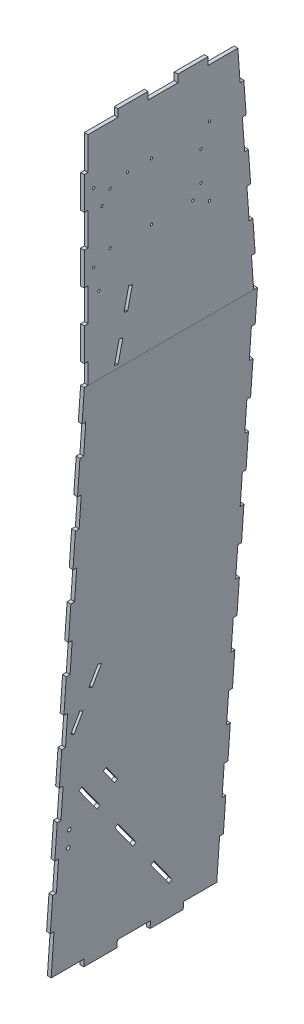
SolidWorks part; units mm, degrees
material "A-Glass Fiber"
ref_plane "Front Plane" through (0, 0, 0) normal (0, 0, 1) x (1, 0, 0)
ref_plane "Top Plane" through (0, 0, 0) normal (0, 1, 0) x (1, 0, 0)
ref_plane "Right Plane" through (0, 0, 0) normal (1, 0, 0) x (0, 0, -1)
sketch "Sketch1" plane through (0, 0, 0) normal (0, 0, 1) x (1, 0, 0)
  line L0 (-215.8818, 2052.32) -> (-215.8818, 1463.04)
  line L1 (-215.8818, 1463.04) -> (-316.0886, 20.32)
  line L2 (-316.0886, 20.32) -> (-317.5, 0)
  line L4 (-215.8818, 2052.32) -> (-215.8818, 2072.64)
  line L6 (-215.8818, 2072.64) -> (-205.7153, 2072.64)
  line L7 (-205.7153, 2072.64) -> (-205.7153, 1463.04)
  line L8 (-205.7153, 1463.04) -> (-307.3335, 0)
  line L9 (-317.5, 0) -> (-307.3335, 0)
  line L10 (-371.5407, 0) -> (-280.9748, 0) construction
  line L13 (-371.5407, 20.32) -> (-280.9748, 20.32) construction
  line L15 (-205.7153, 1463.04) -> (205.7153, 1463.04) construction
  point P23 (-305.9221, 20.32)
  dimension "D1" = 307.3335
extrude "Boss-Extrude1" add sketch "Sketch1" against normal blind 469.9
sketch "Sketch2" plane through (-315.9757, 21.9467, 0) normal (-0.9976, 0.0693, 0) x (0, 0, 1)
  line L35 (0, 1355.6785) -> (0, 0.1049)
  line L37 (-234.95, 1444.5652) -> (-234.95, -21.9996) construction
  line L40 (-10.16, 0.1049) -> (0, 0.1049)
  line L43 (-10.16, 0.1049) -> (-10.16, -21.9996)
  line L46 (0, 1272.0274) -> (-10.16, 1272.0274)
  line L47 (-10.16, 1355.6785) -> (-10.16, 1272.0274)
  line L48 (0, 1355.6785) -> (-10.16, 1355.6785)
  line L49 (0, 1177.9051) -> (-10.16, 1177.9051)
  line L50 (-10.16, 1177.9051) -> (-10.16, 1094.2274)
  line L51 (0, 1094.2274) -> (-10.16, 1094.2274)
  line L52 (0, 916.4274) -> (-10.16, 916.4274)
  line L53 (-10.16, 1000.1317) -> (-10.16, 916.4274)
  line L54 (0, 1000.1317) -> (-10.16, 1000.1317)
  line L55 (0, 822.3583) -> (-10.16, 822.3583)
  line L56 (0, 738.6274) -> (-10.16, 738.6274)
  line L57 (-10.16, 822.3583) -> (-10.16, 738.6274)
  line L58 (0, 644.5849) -> (-10.16, 644.5849)
  line L59 (-10.16, 644.5849) -> (-10.16, 560.8274)
  line L60 (0, 560.8274) -> (-10.16, 560.8274)
  line L61 (0, 466.8115) -> (-10.16, 466.8115)
  line L62 (-10.16, 466.8115) -> (-10.16, 383.0274)
  line L63 (0, 383.0274) -> (-10.16, 383.0274)
  line L64 (0, 289.0381) -> (-10.16, 289.0381)
  line L65 (-10.16, 289.0381) -> (-10.16, 205.2274)
  line L66 (0, 205.2274) -> (-10.16, 205.2274)
  line L67 (0, 111.2647) -> (-10.16, 111.2647)
  line L68 (-10.16, 111.2647) -> (-10.16, 0.1049)
  line L69 (0, 0.1049) -> (-10.16, 0.1049)
  line L70 (-10.16, -21.9996) -> (0, -21.9996)
  line L71 (0, 0.1049) -> (0, -21.9996)
  line L72 (-469.9, 1444.5652) -> (0, 1444.5652) construction
  line L73 (-469.9, -21.9996) -> (0, -21.9996) construction
  line L74 (-469.9, 0.1049) -> (-469.9, -21.9996)
  line L75 (-459.74, -21.9996) -> (-469.9, -21.9996)
  line L76 (-469.9, 0.1049) -> (-459.74, 0.1049)
  line L77 (-459.74, 111.2647) -> (-459.74, 0.1049)
  line L78 (-469.9, 111.2647) -> (-459.74, 111.2647)
  line L79 (-469.9, 205.2274) -> (-459.74, 205.2274)
  line L80 (-459.74, 289.0381) -> (-459.74, 205.2274)
  line L81 (-469.9, 289.0381) -> (-459.74, 289.0381)
  line L82 (-469.9, 383.0274) -> (-459.74, 383.0274)
  line L83 (-459.74, 466.8115) -> (-459.74, 383.0274)
  line L84 (-469.9, 466.8115) -> (-459.74, 466.8115)
  line L85 (-469.9, 560.8274) -> (-459.74, 560.8274)
  line L86 (-459.74, 644.5849) -> (-459.74, 560.8274)
  line L87 (-469.9, 644.5849) -> (-459.74, 644.5849)
  line L88 (-459.74, 822.3583) -> (-459.74, 738.6274)
  line L89 (-469.9, 738.6274) -> (-459.74, 738.6274)
  line L90 (-469.9, 822.3583) -> (-459.74, 822.3583)
  line L91 (-469.9, 1000.1317) -> (-459.74, 1000.1317)
  line L92 (-459.74, 1000.1317) -> (-459.74, 916.4274)
  line L93 (-469.9, 916.4274) -> (-459.74, 916.4274)
  line L94 (-469.9, 1094.2274) -> (-459.74, 1094.2274)
  line L95 (-459.74, 1177.9051) -> (-459.74, 1094.2274)
  line L96 (-469.9, 1177.9051) -> (-459.74, 1177.9051)
  line L97 (-469.9, 1355.6785) -> (-459.74, 1355.6785)
  line L98 (-459.74, 1355.6785) -> (-459.74, 1272.0274)
  line L99 (-469.9, 1272.0274) -> (-459.74, 1272.0274)
  line L100 (-459.74, 0.1049) -> (-459.74, -21.9996)
  line L101 (-459.74, 0.1049) -> (-469.9, 0.1049)
  line L102 (-469.9, 1355.6785) -> (-469.9, 0.1049)
  line L103 (-469.9, 1444.5652) -> (-469.9, -21.9996) construction
  line L104 (-459.74, 205.2274) -> (-469.9, 205.2274) construction
  line M1 (0, -21.9996) -> (0, 1444.5652)
  line M3 (-469.9, 1444.5652) -> (-469.9, -21.9996)
  line M4 (-469.9, -21.9996) -> (0, -21.9996)
extrude "Cut-Extrude1" cut sketch "Sketch2" against normal blind 10.16 contours L66 L35 L64 L65 | L69 L67 L68 M1 | L60 L35 L58 L59 | L63 L35 L61 L62 | L55 L57 L56 L35 | L35 L54 L53 L52 | L51 L35 L49 L50 | L35 L48 L47 L46 | L40 L43 M4 M1 | L100 L76 M3 M4 | L78 L76 L77 M3 | L81 L79 L80 M3 | L84 L82 L83 M3 | L87 L85 L86 M3 | L90 L89 L88 M3 | L93 L92 L91 M3 | L96 L94 L95 M3 | L99 L98 L97 M3 region at (-224.9388, 1332.6419, -464.82) region at (-237.2577, 1155.2825, -464.82) region at (-249.5765, 977.9231, -464.82) region at (-261.8953, 800.5637, -464.82) region at (-274.2142, 623.2043, -464.82) region at (-286.533, 445.8449, -464.82) region at (-298.8518, 268.4855, -464.82) region at (-316.7342, 11.0257, -464.82) region at (-312.1173, 77.4977, -5.08) region at (-298.8518, 268.4855, -5.08) region at (-286.533, 445.8449, -5.08) region at (-274.2142, 623.2043, -5.08) region at (-261.8953, 800.5637, -5.08) region at (-249.5765, 977.9231, -5.08) region at (-237.2577, 1155.2825, -5.08) region at (-224.9388, 1332.6419, -5.08) region at (-316.7342, 11.0257, -5.08) region at (-312.1173, 77.4977, -464.82)
sketch "Sketch3" plane through (-215.8818, 0, 0) normal (-1, 0, 0) x (0, 0, 1)
  line L0 (0, 2052.32) -> (-10.16, 2052.32) construction
  line L1 (0, 1963.42) -> (-10.16, 1963.42) construction
  line L2 (-10.16, 2052.32) -> (-10.16, 1963.42) construction
  line L3 (0, 1874.52) -> (-10.16, 1874.52) construction
  line L4 (0, 1463.04) -> (0, 2072.64)
  line L5 (0, 2072.64) -> (-469.9, 2072.64)
  line L6 (-469.9, 2072.64) -> (-469.9, 1463.04)
  line L8 (0, 1463.04) -> (0, 2072.64)
  line L9 (0, 2072.64) -> (-469.9, 2072.64)
  line L12 (0, 1785.62) -> (-10.16, 1785.62) construction
  line L13 (-10.16, 1874.52) -> (-10.16, 1785.62) construction
  line L14 (0, 1696.72) -> (-10.16, 1696.72) construction
  line L15 (0, 1607.82) -> (-10.16, 1607.82) construction
  line L16 (-10.16, 1696.72) -> (-10.16, 1607.82) construction
  line L17 (0, 1518.92) -> (-10.16, 1518.92) construction
  line L18 (-10.16, 1518.92) -> (-10.16, 1488.44) construction
  line L19 (0, 2052.32) -> (-10.16, 2052.32)
  line L20 (0, 1963.42) -> (-10.16, 1963.42)
  line L21 (-10.16, 2052.32) -> (-10.16, 1963.42)
  line L22 (0, 1874.52) -> (-10.16, 1874.52)
  line L23 (0, 1785.62) -> (-10.16, 1785.62)
  line L24 (-10.16, 1874.52) -> (-10.16, 1785.62)
  line L25 (0, 1696.72) -> (-10.16, 1696.72)
  line L26 (0, 1607.82) -> (-10.16, 1607.82)
  line L27 (-10.16, 1696.72) -> (-10.16, 1607.82)
  line L28 (0, 1518.92) -> (-10.16, 1518.92)
  line L29 (-10.16, 1518.92) -> (-10.16, 1488.44)
  line L30 (0, 2052.32) -> (0, 1463.04)
  line L31 (-234.95, 1463.04) -> (-234.95, 2072.64) construction
  line L32 (-10.16, 2052.32) -> (0, 2052.32)
  line L33 (-10.16, 2052.32) -> (-10.16, 2072.64)
  line L34 (-10.16, 2072.64) -> (0, 2072.64)
  line L35 (0, 2052.32) -> (0, 2072.64)
  line L36 (-469.9, 1463.04) -> (-425.45, 2072.64)
  line L37 (-469.9, 1463.04) -> (-463.754, 1547.3284)
  line L38 (-469.9, 1463.04) -> (-459.7669, 1462.3011)
  line L39 (-463.754, 1547.3284) -> (-453.6209, 1546.5895)
  line L40 (-459.7669, 1462.3011) -> (-453.6209, 1546.5895)
  line L41 (-463.754, 1547.3284) -> (-453.6209, 1546.5895)
  line L42 (-463.754, 1547.3284) -> (-457.6079, 1631.6168)
  line L43 (-453.6209, 1546.5895) -> (-447.4748, 1630.8779)
  line L44 (-457.6079, 1631.6168) -> (-447.4748, 1630.8779)
  line L45 (-457.6079, 1631.6168) -> (-447.4748, 1630.8779)
  line L46 (-457.6079, 1631.6168) -> (-451.4619, 1715.9052)
  line L47 (-447.4748, 1630.8779) -> (-441.3288, 1715.1664)
  line L48 (-451.4619, 1715.9052) -> (-441.3288, 1715.1664)
  line L49 (-451.4619, 1715.9052) -> (-441.3288, 1715.1664)
  line L50 (-451.4619, 1715.9052) -> (-445.3159, 1800.1936)
  line L51 (-441.3288, 1715.1664) -> (-435.1828, 1799.4548)
  line L52 (-445.3159, 1800.1936) -> (-435.1828, 1799.4548)
  line L53 (-445.3159, 1800.1936) -> (-435.1828, 1799.4548)
  line L54 (-10.16, 1488.44) -> (-10.16, 1463.04)
  line L56 (-445.3159, 1800.1936) -> (-439.1699, 1884.4821)
  line L57 (-435.1828, 1799.4548) -> (-429.0368, 1883.7432)
  line L58 (-439.1699, 1884.4821) -> (-429.0368, 1883.7432)
  line L59 (-439.1699, 1884.4821) -> (-429.0368, 1883.7432)
  line L60 (-439.1699, 1884.4821) -> (-433.0238, 1968.7705)
  line L61 (-429.0368, 1883.7432) -> (-422.8907, 1968.0316)
  line L62 (-433.0238, 1968.7705) -> (-422.8907, 1968.0316)
  line L63 (-10.16, 2052.32) -> (-469.9, 2052.32) construction
  line L64 (-469.9, 2072.64) -> (-469.9, 1463.04) construction
  line L65 (-433.0238, 1968.7705) -> (-422.8907, 1968.0316)
  line L66 (-433.0238, 1968.7705) -> (-426.8778, 2053.0589)
  line L67 (-422.8907, 1968.0316) -> (-416.7447, 2052.32)
  line L68 (-426.8778, 2053.0589) -> (-416.7447, 2052.32)
  line L69 (-416.7447, 2052.32) -> (-426.9317, 2052.32)
  line L70 (-426.8778, 2053.0589) -> (-416.7447, 2052.32)
  line L71 (-426.8778, 2053.0589) -> (-425.3531, 2073.9694)
  line L72 (-416.7447, 2052.32) -> (-415.22, 2073.2306)
  line L73 (-425.3531, 2073.9694) -> (-415.22, 2073.2306)
  line L74 (-469.9, 1463.04) -> (0, 1463.04) construction
  line L78 (-469.9, 1463.04) -> (0, 1463.04)
  line L79 (-469.9, 1463.04) -> (0, 1463.04)
  line M7 (0, 1463.04) -> (0, 2072.64)
  line M8 (0, 2072.64) -> (-469.9, 2072.64)
  line M9 (-469.9, 2072.64) -> (-469.9, 1463.04)
  line M10 (-469.9, 1463.04) -> (0, 1463.04)
  dimension "D2" = 44.45
  dimension "D3" = 10.16
  dimension "D1" = 0
extrude "Cut-Extrude2" cut sketch "Sketch3" against normal blind 12.7 contours M10 | L29 L54 L28 M10 M7 | L36 L66 M9 M8 | L48 L36 L44 L47 | L58 L36 L52 L57 | L67 L69 L36 L62 | L25 L27 L26 L8 | L22 L24 L23 L8 | L19 L21 L20 L8 | L33 L19 L8 M8 | L68 L72 L36 M8 | L69 L68 L66 region at (-215.8818, 1490.98, -5.08) region at (-215.8818, 1652.27, -5.08) region at (-215.8818, 1504.9998, -461.7544) region at (-215.8818, 1869.44, -455.0833) region at (-215.8818, 1830.07, -5.08) region at (-215.8818, 1673.3916, -449.4684) region at (-215.8818, 2062.6636, -421.0525) region at (-215.8818, 2007.87, -5.08) region at (-215.8818, 1841.9684, -437.1763) region at (-215.8818, 2052.5663, -423.5181) region at (-215.8818, 2062.48, -5.08) region at (-215.8818, 2010.3602, -424.8903)
sketch "Sketch4" plane through (-215.8818, 0, 0) normal (-1, 0, 0) x (0, 0, 1)
  line L1 (-416.7447, 2072.64) -> (-335.4278, 2072.64)
  line L2 (-416.7447, 2072.64) -> (-416.7447, 2052.32)
  line L3 (-416.7447, 2052.32) -> (-335.4278, 2052.32)
  line L4 (-335.4278, 2072.64) -> (-335.4278, 2052.32)
  line L5 (-10.16, 2072.64) -> (-10.16, 1963.42) construction
  line L6 (-335.4278, 2072.64) -> (-254.1108, 2072.64)
  line L7 (-335.4278, 2072.64) -> (-335.4278, 2052.32)
  line L8 (-335.4278, 2052.32) -> (-254.1108, 2052.32)
  line L9 (-254.1108, 2072.64) -> (-254.1108, 2052.32)
  line L10 (-254.1108, 2072.64) -> (-172.7939, 2072.64)
  line L11 (-254.1108, 2072.64) -> (-254.1108, 2052.32)
  line L12 (-254.1108, 2052.32) -> (-172.7939, 2052.32)
  line L13 (-172.7939, 2072.64) -> (-172.7939, 2052.32)
  line L14 (-172.7939, 2072.64) -> (-91.4769, 2072.64)
  line L15 (-172.7939, 2072.64) -> (-172.7939, 2052.32)
  line L16 (-172.7939, 2052.32) -> (-91.4769, 2052.32)
  line L17 (-91.4769, 2072.64) -> (-91.4769, 2052.32)
  line L18 (-91.4769, 2072.64) -> (-10.16, 2072.64)
  line L19 (-91.4769, 2072.64) -> (-91.4769, 2052.32)
  line L20 (-91.4769, 2052.32) -> (-10.16, 2052.32)
  line L21 (-10.16, 2072.64) -> (-10.16, 2052.32)
  line L23 (-422.8907, 1968.0316) -> (-415.263, 2072.64) construction
  line L24 (-415.263, 2072.64) -> (-10.16, 2072.64) construction
  line M26 (-10.16, 1963.42) -> (-10.16, 2072.64)
  line M27 (-10.16, 2072.64) -> (-415.263, 2072.64)
  dimension "D1" = 20.32
extrude "Cut-Extrude3" cut sketch "Sketch4" against normal blind 12.7 contours L4 L3 M27 | L13 L9 L12 M27 | L17 L20 M26 M27 region at (-215.8818, 2062.48, -376.0862) region at (-215.8818, 2062.48, -213.4523) region at (-215.8818, 2062.48, -50.8185)
sketch "Sketch5" plane through (-315.9757, 21.9467, 0) normal (-0.9976, 0.0693, 0) x (0, 0, 1)
  line L1 (-459.74, -21.9996) -> (-369.824, -21.9996)
  line L2 (-459.74, -21.9996) -> (-459.74, -1.6796)
  line L3 (-459.74, -1.6796) -> (-369.824, -1.6796)
  line L4 (-369.824, -21.9996) -> (-369.824, -1.6796)
  line L5 (-369.824, -21.9996) -> (-279.908, -21.9996)
  line L6 (-369.824, -21.9996) -> (-369.824, -1.6796)
  line L7 (-369.824, -1.6796) -> (-279.908, -1.6796)
  line L8 (-279.908, -21.9996) -> (-279.908, -1.6796)
  line L9 (-279.908, -21.9996) -> (-189.992, -21.9996)
  line L10 (-279.908, -21.9996) -> (-279.908, -1.6796)
  line L11 (-279.908, -1.6796) -> (-189.992, -1.6796)
  line L12 (-189.992, -21.9996) -> (-189.992, -1.6796)
  line L13 (-189.992, -21.9996) -> (-100.076, -21.9996)
  line L14 (-189.992, -21.9996) -> (-189.992, -1.6796)
  line L15 (-189.992, -1.6796) -> (-100.076, -1.6796)
  line L16 (-100.076, -21.9996) -> (-100.076, -1.6796)
  line L17 (-100.076, -21.9996) -> (-10.16, -21.9996)
  line L18 (-100.076, -21.9996) -> (-100.076, -1.6796)
  line L19 (-100.076, -1.6796) -> (-10.16, -1.6796)
  line L20 (-10.16, -21.9996) -> (-10.16, -1.6796)
  line L21 (-10.16, 111.2647) -> (-10.16, -21.9996) construction
  dimension "D1" = 20.32
extrude "Cut-Extrude4" cut sketch "Sketch5" against normal blind 12.7 contours L1 L4 L3 L2 | L9 L12 L11 L8 | L17 L20 L19 L18 L16 region at (-316.796, 10.1356, -414.782) region at (-316.796, 10.1356, -234.95) region at (-316.796, 10.1356, -55.118)
sketch "Sketch6" plane through (-315.9757, 21.9467, 0) normal (-0.9976, 0.0693, 0) x (0, 0, 1)
  line L0 (-217.3726, 211.9965) -> (-163.4402, 285.2141)
  line L1 (-325.2304, 65.5562) -> (-271.298, 138.7738)
  line L2 (-44.1085, 632.6765) -> (-22.5289, 586.4358) construction
  line L3 (-74.8989, 674.6188) -> (-65.6881, 678.9173) construction
  line L8 (-271.6486, 139.032) -> (-279.8219, 145.0526) construction
  line L56 (-87.2678, 725.158) -> (-65.6881, 678.9173) construction
  line L57 (-74.8989, 674.6188) -> (-96.4785, 720.8595) construction
  line L58 (-31.7396, 582.1373) -> (-22.5289, 586.4358) construction
  line L59 (-31.7396, 582.1373) -> (-53.3192, 628.3781) construction
  line L60 (-53.3192, 628.3781) -> (-44.1085, 632.6765) construction
  line L63 (-117.6881, 364.4573) -> (-63.7557, 437.6749) construction
  line L65 (-225.5528, 218.0222) -> (-171.6205, 291.2397) construction
  line L69 (-333.4176, 71.587) -> (-279.4852, 144.8046) construction
  line L70 (-109.5008, 358.4266) -> (-55.5685, 431.6442)
  line L71 (-44.1085, 632.6765) -> (-22.5289, 586.4358)
  line L72 (-74.8989, 674.6188) -> (-65.6881, 678.9173)
  line L73 (-87.2678, 725.158) -> (-65.6881, 678.9173)
  line L74 (-74.8989, 674.6188) -> (-96.4785, 720.8595)
  line L75 (-31.7396, 582.1373) -> (-22.5289, 586.4358)
  line L76 (-31.7396, 582.1373) -> (-53.3192, 628.3781)
  line L77 (-53.3192, 628.3781) -> (-44.1085, 632.6765)
  line L78 (-109.5008, 358.4266) -> (-117.6881, 364.4573)
  line L79 (-55.5685, 431.6442) -> (-63.7557, 437.6749)
  line L80 (-117.6881, 364.4573) -> (-63.7557, 437.6749)
  line L81 (-163.4402, 285.2141) -> (-171.6205, 291.2397)
  line L82 (-225.5528, 218.0222) -> (-171.6205, 291.2397)
  line L83 (-217.3726, 211.9965) -> (-225.5528, 218.0222)
  line L84 (-271.298, 138.7738) -> (-279.4852, 144.8046)
  line L85 (-325.2304, 65.5562) -> (-333.4176, 71.587)
  line L86 (-333.4176, 71.587) -> (-279.4852, 144.8046)
  line L87 (-87.2678, 725.158) -> (-96.4785, 720.8595)
  line L89 (-109.8514, 358.6848) -> (-118.0248, 364.7053) construction
  line L90 (-163.7838, 285.4672) -> (-171.9572, 291.4877) construction
  line L91 (-217.7162, 212.2496) -> (-225.8895, 218.2702) construction
  dimension "D1" = 10.16
extrude "Cut-Extrude5" cut sketch "Sketch6" against normal blind 137.414 contours L73 L87 L74 L72 | L77 L76 L75 L71 | L80 L78 | L83 L81 L82 | L86 L85 L84 region at (-298.541, 272.9601, -194.4965) region at (-308.6877, 126.8743, -302.3578) region at (-288.3947, 419.0407, -86.6283) region at (-273.8885, 627.8938, -37.9241) region at (-267.4804, 720.1529, -81.0833)
sketch "Sketch8" plane through (-215.8818, 0, 0) normal (-1, 0, 0) x (0, 0, 1)
  circle A0 centre (-450.215, 1043.94) radius 9.525 construction
  circle A1 centre (-450.215, 1043.94) radius 9.525
sketch "Sketch13" plane through (-215.8818, 0, 0) normal (-1, 0, 0) x (0, 0, 1)
  line L0 (-413.556, 1633.6344) -> (-413.556, 1614.5844) construction
  line L1 (-270.8715, 1611.4094) -> (-270.8715, 1636.8094) construction
  line L2 (-413.556, 1624.1094) -> (-270.8715, 1624.1094) construction
  line L3 (-270.8715, 1624.1094) -> (-400.856, 1624.1094) construction
  line L4 (-270.8715, 1605.0594) -> (-400.856, 1605.0594) construction
  line L5 (-270.8715, 1643.1594) -> (-400.856, 1643.1594) construction
  line L6 (-416.7447, 2052.32) -> (-335.4278, 2052.32)
  line L7 (-422.8907, 1968.0316) -> (-416.7447, 2052.32)
  circle A0 centre (-25.2465, 1731.87) radius 3.175
  circle A1 centre (-70.409, 1755.42) radius 3.175
  circle A2 centre (-182.409, 1755.42) radius 3.175
  circle A3 centre (-25.2465, 1918.97) radius 3.175
  circle A4 centre (-47.789, 1865.42) radius 3.175
  circle A5 centre (-182.409, 1910.42) radius 3.175
  circle A6 centre (-117.079, 1910.42) radius 3.175
  circle A7 centre (-70.409, 1895.42) radius 3.175
  circle A8 centre (-317.029, 1865.42) radius 3.175
  circle A9 centre (-294.409, 1755.42) radius 3.175
  circle A10 centre (-317.029, 1785.42) radius 3.175
  circle A11 centre (-339.5715, 1731.87) radius 3.175
  circle A12 centre (-339.5715, 1918.97) radius 3.175
  arc A13 (-270.8715, 1605.0594) -> (-270.8715, 1643.1594) centre (-270.8715, 1624.1094) ccw construction
  arc A14 (-400.856, 1643.1594) -> (-400.856, 1605.0594) centre (-400.856, 1624.1094) ccw construction
  point P34 (-335.8637, 1624.1094)
  point P42 (-416.7447, 2052.32)
  dimension "D1" = 12.7
  dimension "D2" = 19.05
extrude "Cut-Extrude8" cut sketch "Sketch13" against normal through all contours L5 A14 L4 A13 | A11 | A10 | A9 | A2 | A1 | A0 | A4 | A7 | A6 | A3 | A5 | A8 | A12 | L0 A14 region at (-215.8818, 1731.87, -25.2465) region at (-215.8818, 1755.42, -70.409) region at (-215.8818, 1755.42, -182.409) region at (-215.8818, 1918.97, -25.2465) region at (-215.8818, 1865.42, -47.789) region at (-215.8818, 1910.42, -182.409) region at (-215.8818, 1910.42, -117.079) region at (-215.8818, 1895.42, -70.409) region at (-215.8818, 1865.42, -317.029) region at (-215.8818, 1755.42, -294.409) region at (-215.8818, 1785.42, -317.029) region at (-215.8818, 1731.87, -339.5715) region at (-215.8818, 1918.97, -339.5715)
sketch "Sketch17" plane through (-215.8818, 0, 0) normal (-1, 0, 0) x (0, 0, 1)
  line L0 (-130.4243, 1639.6605) -> (-120.5247, 1641.946)
  line L1 (-120.5247, 1641.946) -> (-107.584, 1585.8939)
  line L2 (-130.4243, 1639.6605) -> (-117.4836, 1583.6084)
  line L3 (-117.4836, 1583.6084) -> (-107.584, 1585.8939)
  line L4 (-104.543, 1527.5563) -> (-94.6434, 1529.8418)
  line L5 (-91.6023, 1471.5043) -> (-104.543, 1527.5563)
  line L6 (-91.6023, 1471.5043) -> (-81.7027, 1473.7898)
  line L7 (-81.7027, 1473.7898) -> (-94.6434, 1529.8418)
  line L8 (-416.7447, 2052.32) -> (-335.4278, 2052.32)
  line L9 (-422.8907, 1968.0316) -> (-416.7447, 2052.32)
  point P11 (-416.7447, 2052.32)
extrude "Cut-Extrude9" cut sketch "Sketch17" against normal through all contours L6 L7 L4 L5 | L2 L3 L1 L0 region at (-215.8818, 1612.7772, -119.0041) region at (-215.8818, 1500.6731, -93.1229)
sketch "Sketch20" plane through (-315.9757, 21.9467, 0) normal (-0.9976, 0.0693, 0) x (0, 0, 1)
  line L0 (-441.6805, 375.8656) -> (-258.1103, 563.7707)
  line L1 (-258.1103, 563.7707) -> (-341.7803, 797.9819)
  line L2 (-258.1103, 563.7707) -> (-10.16, 315.8204)
  line L3 (-258.1103, 563.7707) -> (-258.6478, 797.9819)
  line L8 (-10.16, 110.1771) -> (-10.16, -1.6796)
  line L9 (-10.16, 466.8115) -> (-10.16, 383.0274) construction
  line L10 (-13.335, 290.1376) -> (-13.335, 359.9876)
  line L11 (-13.335, 290.1376) -> (-48.26, 290.1376)
  line L12 (-13.335, 359.9876) -> (-48.26, 359.9876)
  line L13 (-48.26, 290.1376) -> (-48.26, 359.9876)
  line L32 (-120.9293, 445.7124) -> (-154.8235, 399.6982)
  line L33 (-120.9293, 445.7124) -> (-128.5983, 451.3614)
  line L34 (-154.8235, 399.6982) -> (-162.4926, 405.3473)
  line L35 (-128.5983, 451.3614) -> (-162.4926, 405.3473)
  line L37 (-109.5008, 358.4266) -> (-117.6881, 364.4573) construction
  line L38 (-117.6881, 364.4573) -> (-63.7557, 437.6749) construction
  line L39 (-137.8764, 422.7053) -> (43.6586, 288.9858) construction
  line L40 (-35.56, 332.8883) -> (-35.56, 361.687) construction
  line L41 (-10.16, 466.8115) -> (-10.16, 383.0274)
  circle A0 centre (-35.56, 347.2876) radius 4.7625
  circle A2 centre (-35.56, 302.8376) radius 4.7625
  point P11 (-10.16, -1.6796)
  point P57 (-35.56, 341.2204)
  dimension "D9" = 44.45
  dimension "D15" = 9.525
  dimension "D3" = 3.175
  dimension "D4" = 12.7
  dimension "D5" = 57.15
  dimension "D6" = 317.5
  dimension "D7" = 12.7
  dimension "D8" = 12.7
  dimension "D22" = 9.525
  dimension "D23" = 6.35
  dimension "D24" = 50.8
  dimension "D25" = 34.925
extrude "Cut-Extrude10" cut sketch "Sketch20" against normal through all contours A2 | L2 A0 | L2 A0 | L2 L35 L34 L32 | L33 L35 L2 L32 region at (-285.2619, 464.1454, -128.5379) region at (-286.8509, 441.2683, -145.572) region at (-291.908, 368.4591, -35.5004) region at (-292.1316, 365.2395, -38.7278) region at (-294.992, 324.0565, -35.56)
sketch "Sketch22" [suppressed] plane through (-315.9757, 21.9467, 0) normal (-0.9976, 0.0693, 0) x (0, 0, 1)
  line L3 (-138.6114, 421.183) -> (-138.6114, 431.343)
  line L4 (-138.6114, 431.343) -> (-202.8371, 431.343)
  line L5 (-138.6114, 421.183) -> (-202.8371, 421.183)
  line L6 (-202.8371, 421.183) -> (-202.8371, 431.343)
  line L7 (-267.0629, 421.183) -> (-267.0629, 431.343)
  line L8 (-267.0629, 431.343) -> (-331.2886, 431.343)
  line L9 (-267.0629, 421.183) -> (-331.2886, 421.183)
  line L10 (-331.2886, 421.183) -> (-331.2886, 431.343)
  line L11 (-395.5143, 421.183) -> (-395.5143, 431.343)
  line L12 (-395.5143, 421.183) -> (-459.74, 421.183)
  line L13 (-395.5143, 431.343) -> (-459.74, 431.343)
  line L15 (-459.74, 421.183) -> (-459.74, 431.343)
  line L16 (-100.076, -1.6796) -> (-10.16, -1.6796) construction
  line L17 (-10.16, 111.2647) -> (-10.16, -1.6796) construction
  line L18 (-100.076, -1.6796) -> (-10.16, -1.6796)
  line L19 (-10.16, 111.2647) -> (-10.16, -1.6796)
  point P0 (-10.16, -1.6796)
sketch "Sketch23" plane through (-315.9757, 21.9467, 0) normal (-0.9976, 0.0693, 0) x (0, 0, 1)
  line L2 (-450.215, 1024.4555) -> (-396.5689, 1024.4555) construction
  line L3 (-437.515, 986.3555) -> (-437.515, 1062.5555) construction
  circle A0 centre (-437.515, 986.3555) radius 3.175
  circle A1 centre (-421.64, 1024.4555) radius 3.175
  circle A2 centre (-437.515, 1062.5555) radius 3.175
  point P21 (-437.515, 1024.4555)
  dimension "D1" = 6.35
  dimension "D2" = 28.575
  dimension "D3" = 76.2
  dimension "D4" = 12.7
sketch "Sketch24" plane through (-215.8818, 0, 0) normal (-1, 0, 0) x (0, 0, 1)
  line L0 (-10.16, 1696.72) -> (-10.16, 1607.82) construction
  line L1 (0, 1696.72) -> (-10.16, 1696.72) construction
  circle A0 centre (-39.3138, 1670.4542) radius 18 construction
  circle A1 centre (-39.3138, 1670.4542) radius 18 construction
  circle A2 centre (-39.3137, 1670.4542) radius 3.175
  dimension "D1" = 6.35
  dimension "D2" = 29.1537
  dimension "D3" = 26.2658
extrude "Cut-Extrude12" cut sketch "Sketch24" against normal blind 12.7
